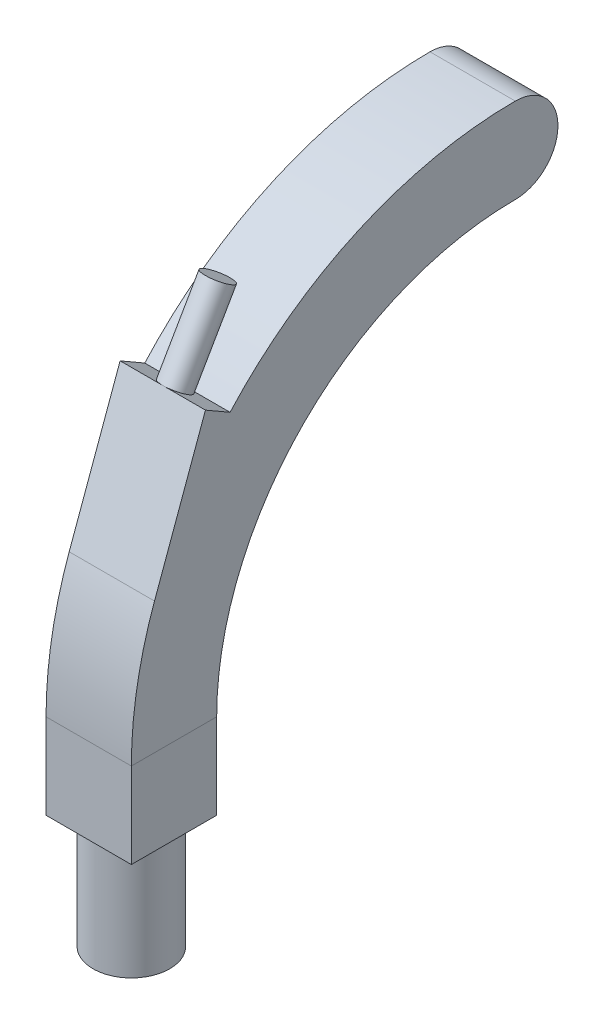
SolidWorks part; units mm, degrees
ref_plane "Front Plane" through (0, 0, 0) normal (0, 0, 1) x (1, 0, 0)
ref_plane "Top Plane" through (0, 0, 0) normal (0, 1, 0) x (1, 0, 0)
ref_plane "Right Plane" through (0, 0, 0) normal (1, 0, 0) x (0, 0, -1)
sketch "Sketch1" plane through (0, 0, 0) normal (1, 0, 0) x (0, 0, -1)
  line L0 (0, 0) -> (0, 30)
  line L1 (0, 30) -> (120, 30) construction
  line L2 (120, 30) -> (120, 150) construction
  arc A0 (120, 150) -> (0, 30) centre (120, 30) ccw
  dimension "D2" = 120
  dimension "D1" = 30
sketch "Sketch2" plane through (0, 0, 0) normal (0, 1, 0) x (1, 0, 0)
  line L1 (-15, -15) -> (15, -15)
  line L2 (-15, -15) -> (-15, 15)
  line L3 (-15, 15) -> (15, 15)
  line L4 (15, -15) -> (15, 15)
  line L5 (-15, -15) -> (15, 15) construction
  line L6 (-15, 15) -> (15, -15) construction
  point P0 (0, 0)
  dimension "D1" = 30
  dimension "D2" = 30
sweep "Sweep1" add profiles "Sketch2" path "Sketch1"
sketch "Sketch3" plane through (0, 0, 0) normal (0, -1, 0) x (1, 0, 0)
  circle A0 centre (0, 0) radius 13.5
  dimension "D1" = 27
extrude "Boss-Extrude1" add sketch "Sketch3" along normal blind 40
sketch "Sketch4" plane through (15, 0, 0) normal (1, 0, 0) x (0, 0, -1)
  line L0 (120, 165) -> (120, 135) construction
  line L1 (120, 165) -> (120, 135)
  arc A0 (120, 135) -> (120, 165) centre (120, 150) ccw
extrude "Boss-Extrude2" add sketch "Sketch4" against normal up to surface (30 mm away) up to face at (-15, 102.4264, -47.5736)
sketch "Sketch5" plane through (0, 0, 0) normal (1, 0, 0) x (0, 0, -1)
  line L0 (120, 165) -> (-15, 165) construction
  line L1 (-15, 165) -> (-15, 30) construction
  line L3 (19.7074, 120.3681) -> (11.0472, 125.3681)
  line L4 (11.0472, 125.3681) -> (-6.8585, 76.1727)
  arc A0 (120, 165) -> (-15, 30) centre (120, 30) ccw construction
  arc A1 (19.7074, 120.3681) -> (-6.8585, 76.1727) centre (120, 30) ccw
  dimension "D5" = 135
  dimension "D1" = 135
  dimension "D2" = 10
  dimension "D3" = 30
  dimension "D4" = 70
extrude "Boss-Extrude3" add sketch "Sketch5" along normal up to surface (15 mm away) and the other way up to surface (15 mm away) up to face at (15, 102.4264, -51.3236) other way up to face at (-15, 102.4264, -51.3236)
sketch "Sketch6" plane through (0, 98.8096, -57.0478) normal (0, 0.866, -0.5) x (1, 0, 0)
  line L0 (0, 0) -> (0, -53.1169) construction
  line L1 (15, -53.1169) -> (-15, -53.1169) construction
  line L2 (15, -48.1169) -> (-15, -48.1169) construction
  line L3 (15, -43.1169) -> (15, -53.1169) construction
  line L4 (-15, -43.1169) -> (-15, -53.1169) construction
  circle A0 centre (0, -48.1169) radius 5
extrude "Boss-Extrude4" add sketch "Sketch6" along normal blind 30
